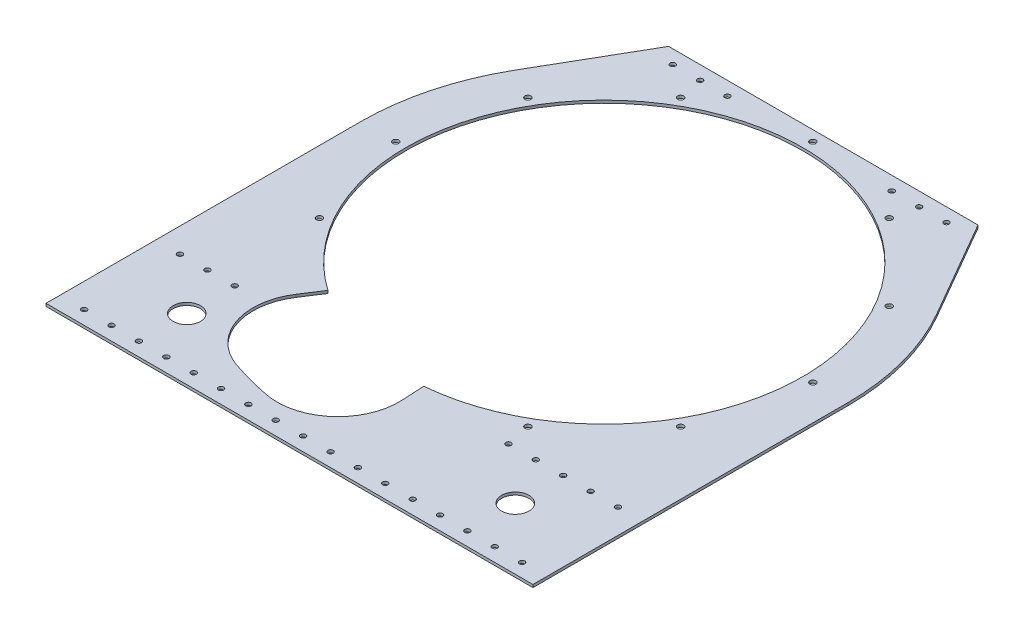
SolidWorks part; units mm, degrees
material "6061-T6 (SS)"
ref_plane "Front Plane" through (0, 0, 0) normal (0, 0, 1) x (1, 0, 0)
ref_plane "Top Plane" through (0, 0, 0) normal (0, 1, 0) x (1, 0, 0)
ref_plane "Right Plane" through (0, 0, 0) normal (1, 0, 0) x (0, 0, -1)
sketch "Sketch1" plane through (0, 0, 0) normal (0, 1, 0) x (1, 0, 0)
  line L1 (269.875, -114.3) -> (-269.875, -114.3)
  line L2 (269.875, -114.3) -> (269.875, 381)
  line L3 (269.875, 381) -> (-269.875, 381)
  line L4 (-269.875, -114.3) -> (-269.875, 381)
  line L5 (-269.875, -71.8706) -> (269.875, -71.8706) construction
  line L6 (139.7, 381) -> (-139.7, 381) construction
  line L9 (-269.875, -111.26) -> (-269.875, -91.94) construction
  line L10 (269.875, -114.3) -> (-269.875, -114.3) construction
  point P0 (0, 0)
  point P19 (0, -71.8706)
extrude "Boss-Extrude1" add sketch "Sketch1" along normal blind 2.54 contours L3 L4 L1 L2
sketch "Sketch2" plane through (0, 2.54, 0) normal (0, 1, 0) x (1, 0, 0)
  line L0 (195.6351, 290.75) -> (99.054, 458.0334)
  line L1 (225.9, 177.8) -> (225.9, -158.139)
  line L2 (99.054, 458.0334) -> (-99.054, 458.0334) construction
  line L3 (-99.054, 458.0334) -> (-195.6351, 290.75)
  line L4 (-480.7152, 488.5224) -> (-512.8473, -198.0528)
  line L5 (225.9, -158.139) -> (-225.9, -158.139) construction
  line L6 (-225.9, -158.139) -> (-225.9, 177.8)
  line L7 (-512.8473, -198.0528) -> (-225.9, -158.139)
  line L8 (-480.7152, 488.5224) -> (-99.054, 458.0334)
  line L9 (99.054, 458.0334) -> (644.55, 478.8644)
  line L10 (644.55, 478.8644) -> (667.5659, -123.8494)
  line L11 (667.5659, -123.8494) -> (225.9, -158.139)
  circle A0 centre (0, 177.8) radius 200.5 construction
  circle A1 centre (0, 177.8) radius 200.5 construction
  arc A2 (225.9, 177.8) -> (195.6351, 290.75) centre (0, 177.8) ccw
  arc A3 (-195.6351, 290.75) -> (-225.9, 177.8) centre (0, 177.8) ccw
  circle A4 centre (0, 177.8) radius 225.9 construction
  circle A5 centre (0, 177.8) radius 184.15
  point P10 (0, 458.0334)
  point P15 (213.2, 177.8)
  dimension "D1" = 25.4
  dimension "D4" = 368.3
  dimension "D2" = 120
extrude "Cut-Extrude1" cut sketch "Sketch2" against normal through all
sketch "Sketch4" plane through (0, 2.54, 0) normal (0, 1, 0) x (1, 0, 0)
  line L0 (17.0921, -27.0045) -> (16.4055, -13.9043)
  line L1 (-110.0597, 19.982) -> (-117.2044, 8.9802)
  line L2 (10.7508, -27.3368) -> (10.0642, -14.2366)
  line L3 (-104.7342, 16.5235) -> (-111.8788, 5.5217)
  line L4 (10.7508, -27.3368) -> (10.0642, -14.2366) construction
  line L5 (-104.7342, 16.5235) -> (-111.8788, 5.5217) construction
  line L6 (195.6351, 290.75) -> (143.5293, 381)
  line L7 (143.5293, 381) -> (-143.5293, 381)
  line L8 (-143.5293, 381) -> (-195.6351, 290.75)
  line L9 (-225.9, 177.8) -> (-225.9, -114.3)
  line L10 (-225.9, -114.3) -> (225.9, -114.3)
  line L11 (225.9, -114.3) -> (225.9, 177.8)
  line L12 (195.6351, 290.75) -> (143.5293, 381)
  line L13 (143.5293, 381) -> (-143.5293, 381)
  line L14 (-143.5293, 381) -> (-195.6351, 290.75)
  line L15 (-225.9, 177.8) -> (-225.9, -114.3)
  line L16 (-225.9, -114.3) -> (225.9, -114.3)
  line L17 (225.9, -114.3) -> (225.9, 177.8)
  line L19 (225.9, -114.3) -> (-225.9, -114.3) construction
  arc A0 (-117.2044, 8.9802) -> (-88.464, -75.1467) centre (-69.8069, -21.8001) ccw
  arc A1 (-88.464, -75.1467) -> (-49.8612, -85.4903) centre (0, 177.8) ccw
  arc A2 (-195.6351, 290.75) -> (-225.9, 177.8) centre (0, 177.8) ccw
  arc A3 (225.9, 177.8) -> (195.6351, 290.75) centre (0, 177.8) ccw
  arc A4 (-195.6351, 290.75) -> (-225.9, 177.8) centre (0, 177.8) ccw
  arc A5 (225.9, 177.8) -> (195.6351, 290.75) centre (0, 177.8) ccw
  arc A6 (-49.8612, -85.4903) -> (17.0921, -27.0045) centre (-39.3455, -29.9622) ccw
  arc A7 (16.4055, -13.9043) -> (3.4772, -1.8714) centre (3.7229, -14.569) ccw
  arc A8 (-92.847, 23.9386) -> (3.4772, -1.8714) centre (0, 177.8) ccw
  arc A9 (-92.847, 23.9386) -> (-110.0597, 19.982) centre (-99.4086, 13.065) ccw
  arc A10 (-48.6797, -79.2512) -> (10.7508, -27.3368) centre (-39.3455, -29.9622) ccw
  arc A11 (10.0642, -14.2366) -> (3.6, -8.2202) centre (3.7229, -14.569) ccw
  arc A12 (-96.1278, 18.5018) -> (3.6, -8.2202) centre (0, 177.8) ccw
  arc A13 (-96.1278, 18.5018) -> (-104.7342, 16.5235) centre (-99.4086, 13.065) ccw
  arc A14 (-111.8788, 5.5217) -> (-86.3677, -69.1527) centre (-69.8069, -21.8001) ccw
  arc A15 (-86.3677, -69.1527) -> (-48.6797, -79.2512) centre (0, 177.8) ccw
  arc A16 (-48.6797, -79.2512) -> (10.7508, -27.3368) centre (-39.3455, -29.9622) ccw construction
  arc A17 (10.0642, -14.2366) -> (3.6, -8.2202) centre (3.7229, -14.569) ccw construction
  arc A18 (-96.1278, 18.5018) -> (3.6, -8.2202) centre (0, 177.8) ccw construction
  arc A19 (-96.1278, 18.5018) -> (-104.7342, 16.5235) centre (-99.4086, 13.065) ccw construction
  arc A20 (-111.8788, 5.5217) -> (-86.3677, -69.1527) centre (-69.8069, -21.8001) ccw construction
  arc A21 (-86.3677, -69.1527) -> (-48.6797, -79.2512) centre (0, 177.8) ccw construction
  dimension "D1" = 0
  dimension "D2" = 0
  dimension "D3" = 6.35
extrude "Cut-Extrude3" cut sketch "Sketch4" against normal through all both and the other way through all flip side to cut
other "DeleteFace1" face at (-106.8112, 1.27, -22.907) face at (15.0547, 1.27, 9.7469) and patch yes
hole_wizard "#8 Clearance Hole1" positions "Sketch5" profile "Sketch6" hole size "#8" standard "ANSI Inch" end condition through all
sketch "Sketch5" plane through (0, 2.54, 0) normal (0, 1, 0) x (1, 0, 0)
  circle A0 centre (203.2, -12.7) radius 2.0701 construction
  arc A1 (124.9313, 368.2238) -> (129.0687, 368.2238) centre (127, 368.3) ccw construction
  arc A2 (99.5313, 368.2238) -> (103.6687, 368.2238) centre (101.6, 368.3) ccw construction
  arc A3 (74.1313, 368.2238) -> (78.2687, 368.2238) centre (76.2, 368.3) ccw construction
  arc A9 (-78.2687, 368.2238) -> (-74.1313, 368.2238) centre (-76.2, 368.3) ccw construction
  arc A10 (-103.6687, 368.2238) -> (-99.5313, 368.2238) centre (-101.6, 368.3) ccw construction
  arc A11 (-129.0687, 368.2238) -> (-124.9313, 368.2238) centre (-127, 368.3) ccw construction
  point P0 (127, -101.6)
  point P2 (101.6, -101.6)
  point P4 (76.2, -101.6)
  point P14 (50.8, -101.6)
  point P17 (25.4, -101.6)
  point P20 (0, -101.6)
  point P23 (-25.4, -101.6)
  point P26 (-50.8, -101.6)
  point P29 (-76.2, -101.6)
  point P32 (-101.6, -101.6)
  point P35 (-127, -101.6)
  point P38 (-152.4, -101.6)
  point P41 (-177.8, -101.6)
  point P44 (-203.2, -101.6)
  point P47 (-152.4, -12.7)
  point P50 (-177.8, -12.7)
  point P53 (-203.2, -12.7)
  point P56 (101.6, -12.7)
  point P59 (127, -12.7)
  point P62 (152.4, -12.7)
  point P66 (152.4, -101.6)
  point P68 (177.8, -101.6)
  point P70 (203.2, -101.6)
  point P81 (203.2, -12.7)
  point P83 (177.8, -12.7)
  point P102 (127, 368.3)
  point P104 (101.6, 368.3)
  point P106 (76.2, 368.3)
  point P118 (-76.2, 368.3)
  point P120 (-101.6, 368.3)
  point P122 (-127, 368.3)
sketch "Sketch6" plane through (127, 2.54, 101.6) normal (1, 0, 0) x (0, 0, 1)
  line L0 (0, 0) -> (0, 2.54)
  line L1 (0, 2.54) -> (2.4574, 2.54)
  line L2 (2.4574, 2.54) -> (2.4574, 0)
  line L5 (2.4574, 0) -> (0, 0)
  line L11 (0, -6.35) -> (0, 107.95) construction
  dimension "Thru Hole Dia." = 4.9149
  dimension "Thru Hole Depth" = 2.54
hole_wizard "#10 Clearance Hole1" positions "Sketch8" profile "Sketch9" hole size "#10" standard "ANSI Inch" end condition through all
sketch "Sketch8" plane through (0, 2.54, 0) normal (0, 1, 0) x (1, 0, 0)
  circle A0 centre (96.75, 10.2241) radius 2.65 construction
  circle A1 centre (167.5759, 81.05) radius 2.65 construction
  circle A2 centre (193.5, 177.8) radius 2.65 construction
  circle A3 centre (167.5759, 274.55) radius 2.65 construction
  circle A4 centre (96.75, 345.3759) radius 2.65 construction
  circle A5 centre (0, 371.3) radius 2.65 construction
  circle A6 centre (-96.75, 345.3759) radius 2.65 construction
  circle A7 centre (-167.5759, 274.55) radius 2.65 construction
  circle A8 centre (-193.5, 177.8) radius 2.65 construction
  circle A9 centre (-167.5759, 81.05) radius 2.65 construction
  point P0 (-167.5759, 274.55)
  point P2 (-96.75, 345.3759)
  point P4 (0, 371.3)
  point P6 (96.75, 345.3759)
  point P8 (167.5759, 274.55)
  point P10 (193.5, 177.8)
  point P12 (167.5759, 81.05)
  point P14 (96.75, 10.2241)
  point P16 (-167.5759, 81.05)
  point P18 (-193.5, 177.8)
sketch "Sketch9" plane through (-167.5759, 2.54, -274.55) normal (1, 0, 0) x (0, 0, 1)
  line L0 (0, 0) -> (0, 2.54)
  line L1 (0, 2.54) -> (2.8067, 2.54)
  line L2 (2.8067, 2.54) -> (2.8067, 0)
  line L5 (2.8067, 0) -> (0, 0)
  line L11 (0, -6.35) -> (0, 107.95) construction
  dimension "Thru Hole Dia." = 5.6134
  dimension "Thru Hole Depth" = 2.54
sketch "Sketch10" plane through (0, 2.54, 0) normal (0, 1, 0) x (1, 0, 0)
  line L0 (-152.4, -57.15) -> (152.4, -57.15) construction
  line L1 (0, -1.397) -> (0, 1.397) construction
  line L2 (-152.4, -101.6) -> (-152.4, -12.7) construction
  circle A0 centre (-152.4, -57.15) radius 12.7
  circle A1 centre (152.4, -57.15) radius 12.7
  circle A2 centre (-152.4, -101.6) radius 2.4574 construction
  circle A4 centre (-152.4, -12.7) radius 2.4574 construction
  point P6 (0, -57.15)
  point P18 (-152.4, -57.15)
  dimension "D2" = 25.4
  dimension "D1" = 304.8
extrude "Cut-Extrude4" cut sketch "Sketch10" against normal through all
